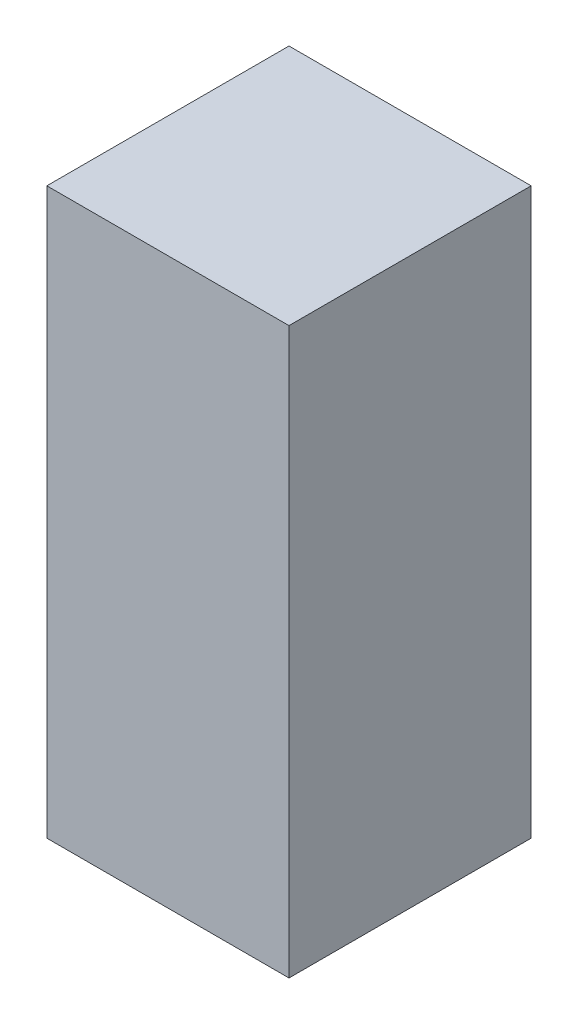
SolidWorks part; units mm, degrees
ref_plane "Front Plane" through (0, 0, 0) normal (1, 0, 0) x (0, 1, 0)
ref_plane "Top Plane" through (0, 0, 0) normal (0, 0, 1) x (0, 1, 0)
ref_plane "Right Plane" through (0, 0, 0) normal (0, 1, 0) x (-1, 0, 0)
sketch "Sketch1" plane through (0, 0, 0) normal (0, 0, 1) x (0, 1, 0)
  line L1 (0, 0) -> (77, 0)
  line L2 (0, 0) -> (0, 33)
  line L3 (0, 33) -> (77, 33)
  line L4 (77, 0) -> (77, 33)
  dimension "D1" = 77
  dimension "D2" = 33
extrude "Boss-Extrude1" add sketch "Sketch1" along normal blind 33
